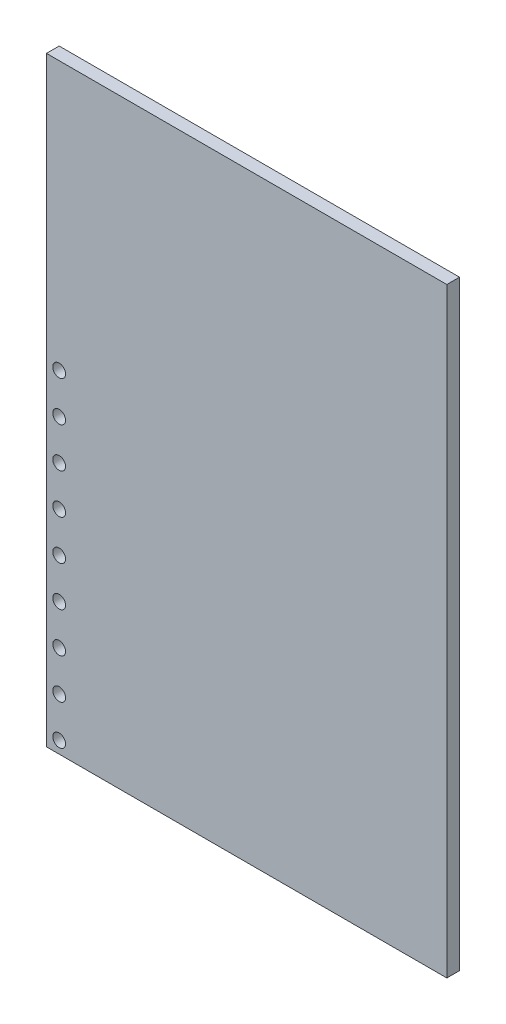
SolidWorks part; units mm, degrees
ref_plane "Front Plane" through (0, 0, 0) normal (0, 0, 1) x (1, 0, 0)
ref_plane "Top Plane" through (0, 0, 0) normal (0, 1, 0) x (1, 0, 0)
ref_plane "Right Plane" through (0, 0, 0) normal (1, 0, 0) x (0, 0, -1)
sketch "Sketch1" plane through (0, 0, 0) normal (0, 1, 0) x (1, 0, 0)
  line L1 (0, 0) -> (100, 0)
  line L2 (0, 0) -> (0, 3.175)
  line L3 (0, 3.175) -> (100, 3.175)
  line L4 (100, 0) -> (100, 3.175)
  dimension "D1" = 100
  dimension "D2" = 3.175
extrude "Boss-Extrude1" add sketch "Sketch1" along normal blind 150
sketch "Sketch2" plane through (0, 0, 0) normal (0, 0, 1) x (1, 0, 0)
  line L5 (0, 0) -> (6.35, 0)
  line L6 (0, 0) -> (0, 20)
  line L12 (0, 150) -> (0, 0) construction
  line L13 (0, 30) -> (0, 54)
  line L14 (0, 150) -> (0, 0) construction
  line L16 (0, 30) -> (0, 40)
  line L17 (0, 40) -> (0, 50)
  line L18 (0, 50) -> (0, 54)
  circle A4 centre (3.175, 3) radius 1.6
  circle A5 centre (3.175, 13) radius 1.6
  circle A6 centre (3.175, 23) radius 1.6
  circle A7 centre (3.175, 63) radius 1.6
  circle A8 centre (3.175, 43) radius 1.6
  circle A9 centre (3.175, 33) radius 1.6
  circle A10 centre (3.175, 83) radius 1.6
  circle A11 centre (3.175, 73) radius 1.6
  circle A12 centre (3.175, 53) radius 1.6
  dimension "D5" = 10
  dimension "D6" = 3
  dimension "D7" = 10
  dimension "D3" = 10
  dimension "D4" = 3.2
  dimension "D12" = 3.2
  dimension "D13" = 3.2
  dimension "D14" = 3.2
  dimension "D15" = 3.2
  dimension "D16" = 3.2
  dimension "D17" = 3.2
  dimension "D18" = 3.2
  dimension "D19" = 3.2
  dimension "D1" = 10
  dimension "D2" = 10
  dimension "D8" = 3.175
  dimension "D9" = 10
  dimension "D10" = 10
  dimension "D11" = 10
extrude "Cut-Extrude2" cut sketch "Sketch2" against normal blind 5 contours A10
extrude "Cut-Extrude3" cut sketch "Sketch2<14>" against normal blind 5 contours A11
sketch "Sketch2<14>" plane through (0, 0, 0) normal (0, 0, 1) x (1, 0, 0) same geometry as "Sketch2"
extrude "Cut-Extrude4" cut sketch "Sketch2<15>" against normal blind 5 contours A12
sketch "Sketch2<15>" plane through (0, 0, 0) normal (0, 0, 1) x (1, 0, 0) same geometry as "Sketch2"
extrude "Cut-Extrude5" cut sketch "Sketch2<16>" against normal blind 5 contours A7
sketch "Sketch2<16>" plane through (0, 0, 0) normal (0, 0, 1) x (1, 0, 0) same geometry as "Sketch2"
extrude "Cut-Extrude6" cut sketch "Sketch2<17>" against normal blind 5 contours A8
sketch "Sketch2<17>" plane through (0, 0, 0) normal (0, 0, 1) x (1, 0, 0) same geometry as "Sketch2"
extrude "Cut-Extrude7" cut sketch "Sketch2<18>" against normal blind 5 contours A9
sketch "Sketch2<18>" plane through (0, 0, 0) normal (0, 0, 1) x (1, 0, 0) same geometry as "Sketch2"
extrude "Cut-Extrude8" cut sketch "Sketch2<19>" against normal blind 5 contours A6
sketch "Sketch2<19>" plane through (0, 0, 0) normal (0, 0, 1) x (1, 0, 0) same geometry as "Sketch2"
extrude "Cut-Extrude9" cut sketch "Sketch2<20>" against normal blind 5 contours A5
sketch "Sketch2<20>" plane through (0, 0, 0) normal (0, 0, 1) x (1, 0, 0) same geometry as "Sketch2"
extrude "Cut-Extrude10" cut sketch "Sketch2<21>" against normal blind 5 contours A4
sketch "Sketch2<21>" plane through (0, 0, 0) normal (0, 0, 1) x (1, 0, 0) same geometry as "Sketch2"
